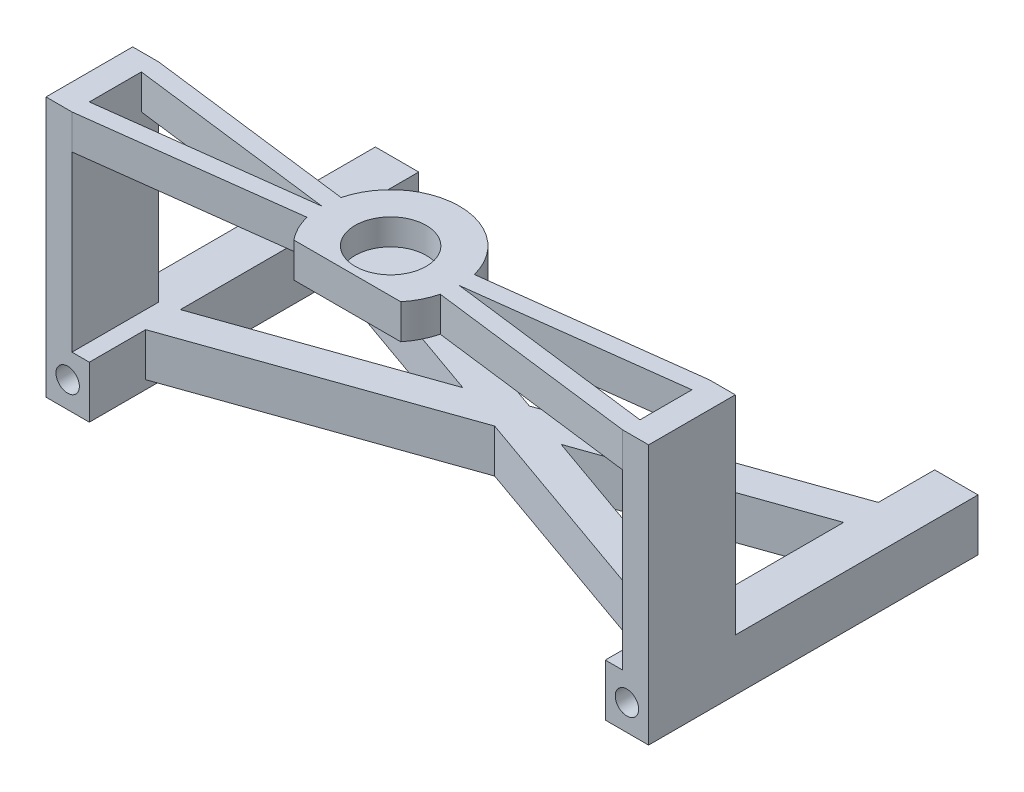
SolidWorks part; units mm, degrees
ref_plane "Front Plane" through (0, 0, 0) normal (0, 0, 1) x (1, 0, 0)
ref_plane "Top Plane" through (0, 0, 0) normal (0, 1, 0) x (1, 0, 0)
ref_plane "Right Plane" through (0, 0, 0) normal (1, 0, 0) x (0, 0, -1)
sketch "Sketch1" plane through (0, 0, 0) normal (0, 1, 0) x (1, 0, 0)
  line L0 (32.26, 0) -> (32.26, 4.019) construction
  line L1 (0, 0) -> (64.52, 0)
  line L2 (0, 0) -> (0, 25)
  line L3 (0, 25) -> (64.52, 25)
  line L4 (64.52, 0) -> (64.52, 25)
  line L5 (-2.5, 31.5) -> (2.5, 31.5)
  line L6 (-2.5, 31.5) -> (-2.5, -6.5)
  line L7 (-2.5, -6.5) -> (2.5, -6.5)
  line L8 (2.5, 31.5) -> (2.5, -6.5)
  line L9 (0, 12.5) -> (7.5775, 12.5) construction
  line L10 (0, 0) -> (0, -8.8754) construction
  line L11 (62.02, 31.5) -> (62.02, -6.5)
  line L12 (67.02, -6.5) -> (62.02, -6.5)
  line L13 (67.02, 31.5) -> (67.02, -6.5)
  line L14 (67.02, 31.5) -> (62.02, 31.5)
  line L15 (2.5, 0) -> (62.02, 21)
  line L16 (62.02, 25) -> (2.5, 4)
  line L17 (2.5, 25) -> (62.02, 4)
  line L18 (62.02, 0) -> (2.5, 21)
  point P11 (0, 12.5)
  point P12 (2.5, 12.5)
  point P13 (0, 31.5)
  point P21 (64.52, 31.5)
  point P22 (62.02, 12.5)
  point P23 (64.52, 12.5)
  dimension "D1" = 64.52
  dimension "D2" = 25
  dimension "D3" = 5
  dimension "D4" = 38
  dimension "D5" = 4
  dimension "D6" = 4
extrude "Boss-Extrude1" add sketch "Sketch1" along normal blind 5 contours L8 L5 L6 L7 L1 L2 L3 | L8 L3 L2 L1 | L18 L16 L17 L8 | L18 L15 L17 L16 | L16 L17 L15 L11 | L15 L18 L16 L8 | L18 L11 L17 L15 | L13 L14 L11 L3 L4 L1 L12 | L3 L11 L1 L4 region at (1.25, 0, -12.5) region at (-0.6127, 0, -12.5) region at (16.0126, 0, -6.6974) region at (63.27, 0, -12.5) region at (48.5074, 0, -6.6974) region at (65.1327, 0, -12.5) region at (32.26, 0, -12.5) region at (16.0126, 0, -18.3026) region at (48.5074, 0, -18.3026)
extrude "Boss-Extrude2" add sketch "Sketch1<3>" against normal blind 1 contours L8 L3 L2 L1 | L8 L5 L6 L7 L1 L2 L3 | L3 L11 L1 L4 | L13 L14 L11 L3 L4 L1 L12 region at (1.25, 0, -12.5) region at (-0.6127, 0, -12.5) region at (63.27, 0, -12.5) region at (65.1327, 0, -12.5)
sketch "Sketch1<3>" plane through (0, 0, 0) normal (0, 1, 0) x (1, 0, 0) same geometry as "Sketch1"
sketch "Sketch2" plane through (0, 0, -31.5) normal (0, 0, -1) x (-1, 0, 0)
  line L0 (-32.26, 5) -> (-32.26, 0) construction
  line L1 (-32.26, 5) -> (-32.26, 0)
  line L2 (-2.5, -1) -> (2.5, 5) construction
  line L4 (2.5, 5) -> (-2.5, 5)
  line L5 (2.5, -1) -> (2.5, 5)
  line L6 (-2.5, -1) -> (2.5, -1)
  line L7 (-2.5, 5) -> (-2.5, -1)
  line L9 (2.5, -1) -> (2.5, 5)
  line L10 (-2.5, -1) -> (2.5, -1)
  line L11 (-2.5, 5) -> (-2.5, -1)
  line L15 (2.5, 5) -> (-2.5, 5)
  circle A0 centre (0, 2) radius 1.35
  circle A1 centre (-64.52, 2) radius 1.35
  dimension "D2" = 2.7
  dimension "D1" = 0
extrude "Cut-Extrude1" cut sketch "Sketch2" against normal through all contours L2 A0 | A0 L2 | A1 region at (0.4402, 2.3668, -31.5) region at (-0.4402, 1.6332, -31.5)
sketch "Sketch3" plane through (0, -1, 0) normal (0, -1, 0) x (-1, 0, 0)
  line L0 (-32.26, -30.9894) -> (-32.26, 10.5)
  line L3 (2.5, 3.5) -> (2.5, -6.5)
  line L7 (2.5, -6.5) -> (-0.5, -6.5) construction
  line L9 (2.5, 3.5) -> (-0.5, 3.5)
  line L14 (-0.5, -6.5) -> (-0.5, 3.5)
  line L15 (2.5, -6.5) -> (-0.5, -6.5)
  line L17 (2.5, 3.5) -> (-0.5, 3.5)
  line L21 (-67.02, -6.5) -> (-64.02, -6.5) construction
  line L22 (-67.02, 3.5) -> (-64.02, 3.5)
  line L23 (-67.02, -6.5) -> (-64.02, -6.5)
  line L24 (-64.02, -6.5) -> (-64.02, 3.5)
  line L25 (-67.02, 3.5) -> (-64.02, 3.5)
  line L26 (-67.02, 3.5) -> (-67.02, -6.5)
  line M52 (2.5, -6.5) -> (2.5, 31.5)
  dimension "D1" = 3
  dimension "D2" = 10
extrude "Boss-Extrude3" add sketch "Sketch3" against normal blind 20 from surface contours L7 L9 M52 | L22 L26 L23 L24 region at (-1, -1, 1.5) region at (65.52, -1, 1.5) starting at face at (32.26, 5, -12.5)
sketch "Sketch4" plane through (0, 25, 0) normal (0, -1, 0) x (-1, 0, 0)
  line L0 (-0.5, 1.5) -> (-24.32, -1.5)
  line L6 (-0.5, -6.5) -> (-32.26, -2.5)
  line L7 (-0.5, -4.5) -> (-24.32, -1.5)
  line L8 (-32.26, -2.5) -> (-64.02, -6.5)
  line L9 (-40.2, -1.5) -> (-64.02, -4.5)
  line L10 (-40.2, -1.5) -> (-64.02, 1.5)
  line L11 (-32.26, -0.5) -> (-64.02, 3.5)
  line L12 (-0.5, 3.5) -> (2.5, 3.5) construction
  line L13 (-64.02, -4.5) -> (-64.02, -6.5) construction
  line L14 (-64.02, 3.5) -> (-64.02, 1.5) construction
  line L15 (-0.5, -4.5) -> (-0.5, -6.5) construction
  line L16 (-0.5, 3.5) -> (-0.5, 1.5) construction
  line L17 (-0.5, 3.5) -> (2.5, 3.5)
  line L18 (2.5, 3.5) -> (2.5, -6.5)
  line L19 (2.5, -6.5) -> (-0.5, -6.5)
  line L20 (-0.5, -4.5) -> (-0.5, 1.5)
  line L21 (-67.02, 3.5) -> (-64.02, 3.5)
  line L22 (-64.02, 1.5) -> (-64.02, -4.5)
  line L23 (-64.02, -6.5) -> (-67.02, -6.5)
  line L24 (-67.02, -6.5) -> (-67.02, 3.5)
  line L25 (-0.5, 3.5) -> (-32.26, -0.5)
  line L26 (-64.02, 3.5) -> (-67.02, 3.5) construction
  line L27 (2.5, -6.5) -> (-0.5, -6.5) construction
  line L28 (-64.02, -6.5) -> (-67.02, -6.5) construction
  dimension "D1" = 2
extrude "Boss.-Extru.1" add sketch "Sketch4" against normal blind 4
sketch "Esquisse1" plane through (0, 29, 0) normal (0, 1, 0) x (1, 0, 0)
  line L0 (24.32, -1.5) -> (40.2, -1.5) construction
  line L2 (-22.2061, -6.5) -> (86.7261, -6.5) construction
  line L3 (26.0921, -6.5) -> (38.4279, -6.5)
  circle A0 centre (32.26, -1.5) radius 4.1
  arc A2 (38.4279, -6.5) -> (26.0921, -6.5) centre (32.26, -1.5) ccw
  point P12 (38.4279, -6.5)
  line M9 (32.26, -0.5) -> (0.5, 3.5)
  line M13 (0.5, -6.5) -> (32.26, -2.5)
  line M14 (32.26, -2.5) -> (64.02, -6.5)
  line M18 (64.02, 3.5) -> (32.26, -0.5)
  dimension "D1" = 8.2
extrude "Boss.-Extru.2" add sketch "Esquisse1" against normal blind 4 contours L3 A2 A0 M14 M13 | L0 A2 A0 M13 | A2 L0 A0 M9 | A2 A0 M18 M9 | A0 L0 A2 M18 | L0 A0 A2 M14 | L0 A0 M13 M14 | A0 L0 M18 M9 | A0 M18 M9 | A0 M13 M14
sketch "Esquisse2" plane through (0, 29, 0) normal (0, 1, 0) x (1, 0, 0)
  circle A0 centre (32.26, -1.5) radius 4.1
  dimension "D1" = 8.2
extrude "Enlèv. mat.-Extru.1" cut sketch "Esquisse2" against normal blind 3
